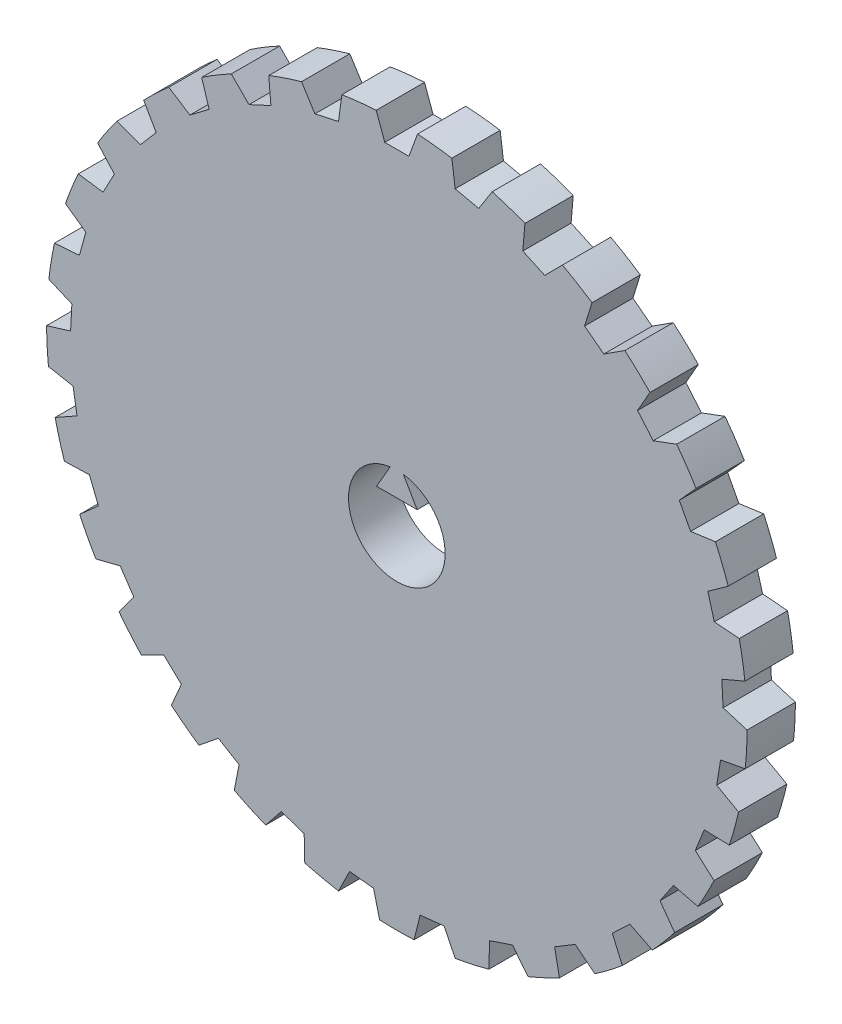
SolidWorks part; units mm, degrees
ref_plane "前视基准面" through (0, 0, 0) normal (0, 0, 1) x (1, 0, 0)
ref_plane "上视基准面" through (0, 0, 0) normal (0, 1, 0) x (1, 0, 0)
ref_plane "右视基准面" through (0, 0, 0) normal (1, 0, 0) x (0, 0, -1)
sketch "Sketch1" plane through (0, 0, 0) normal (0, 0, 1) x (1, 0, 0)
  line L0 (0, 0.1709) -> (0, 50000.1709) construction
  line L1 (-0.0684, 0.4953) -> (-0.21, 0.25)
  line L2 (-0.21, 0.25) -> (0.21, 0.25)
  line L3 (0.21, 0.25) -> (0.0684, 0.4953)
  line L4 (-0.2137, 3.6187) -> (-0.125, 3.375)
  line L5 (-0.125, 3.375) -> (0.125, 3.375)
  line L6 (0.125, 3.375) -> (0.2137, 3.6187)
  circle A0 centre (0, 0) radius 3.625
  arc A1 (-0.0684, 0.4953) -> (0.0684, 0.4953) centre (0, 0) ccw
  point P8 (0, 0)
  dimension "D1" = 7.25
  dimension "D2" = 0.42
  dimension "D6" = 0.5
  dimension "D3" = 30
  dimension "D4" = 30
  dimension "D5" = 0.25
  dimension "D7" = 0.25
  dimension "D8" = 20
  dimension "D9" = 20
  dimension "D10" = 3.375
extrude "Boss-Extrude2" add sketch "Sketch1" along normal blind 0.5 contours A0 L0 A1 L1 L2 L5 L4 | L0 A0 L6 L5 L2 L3 A1 | L0 L5 L6 A0 | L5 L0 A0 L4 region at (0.0625, 3.2725, 0) region at (-0.0865, 3.5099, 0) region at (0.0865, 3.5099, 0)
extrude "Cut-Extrude1" cut sketch "Sketch1<3>" against normal through all and the other way through all contours L0 L5 L6 A0 | L5 L0 A0 L4 region at (-0.0865, 3.5099, 0) region at (0.0865, 3.5099, 0)
sketch "Sketch1<3>" plane through (0, 0, 0) normal (0, 0, 1) x (1, 0, 0) same geometry as "Sketch1"
pattern_circular "CirPattern1" count 29 over 360 about axis through (0, 0, 0.5) along (0, 0, -1) of "Cut-Extrude1"
